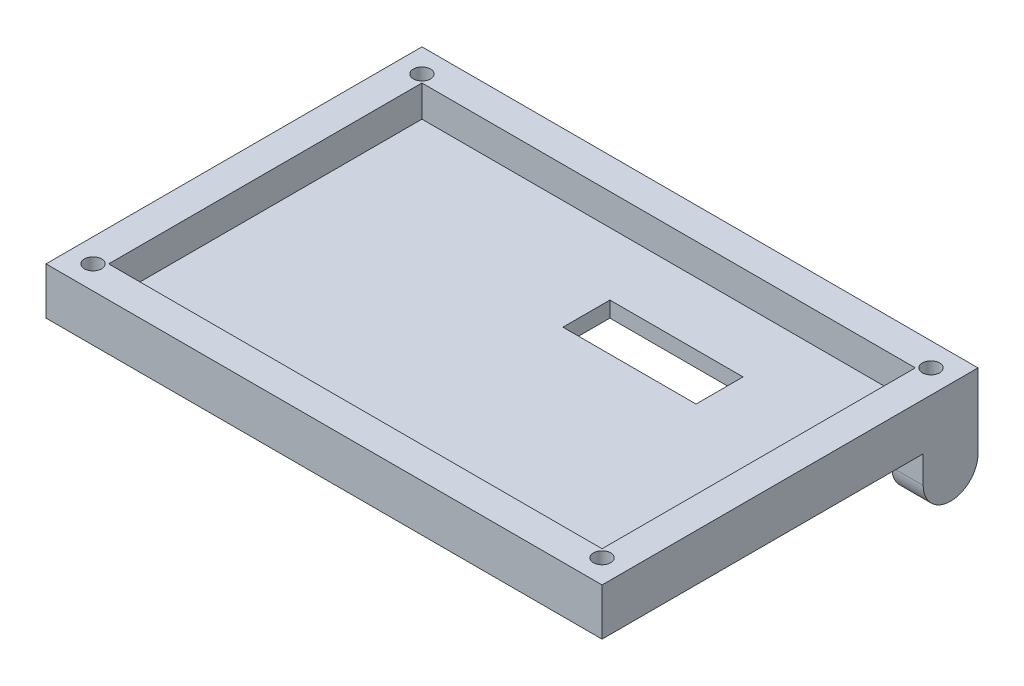
SolidWorks part; units mm, degrees
ref_plane "前视基准面" through (0, 0, 0) normal (0, 0, 1) x (1, 0, 0)
ref_plane "上视基准面" through (0, 0, 0) normal (0, 1, 0) x (1, 0, 0)
ref_plane "右视基准面" through (0, 0, 0) normal (1, 0, 0) x (0, 0, -1)
sketch "草图1" plane through (0, 0, 0) normal (0, 1, 0) x (1, 0, 0)
  line L1 (-17.75, 12) -> (17.75, 12)
  line L2 (-17.75, 12) -> (-17.75, -12)
  line L3 (-17.75, -12) -> (17.75, -12)
  line L4 (17.75, 12) -> (17.75, -12)
  line L5 (-17.75, 12) -> (17.75, -12) construction
  line L6 (-17.75, -12) -> (17.75, 12) construction
  point P0 (0, 0)
  dimension "D1" = 24
  dimension "D2" = 35.5
extrude "凸台-拉伸1" add sketch "草图1" along normal blind 3
sketch "草图2" plane through (0, 3, 0) normal (0, 1, 0) x (1, 0, 0)
  line L0 (17.75, 12) -> (-17.75, 12) construction
  line L1 (-15.75, 10) -> (15.75, 10)
  line L2 (-15.75, 10) -> (-15.75, -10)
  line L3 (-15.75, -10) -> (15.75, -10)
  line L4 (15.75, 10) -> (15.75, -10)
  line L5 (-15.75, 10) -> (15.75, -10) construction
  line L6 (-15.75, -10) -> (15.75, 10) construction
  line L7 (-17.75, 12) -> (-17.75, -12) construction
  point P0 (0, 0)
  dimension "D1" = 2
  dimension "D2" = 2
extrude "切除-拉伸1" cut sketch "草图2" against normal blind 2
sketch "草图3" plane through (0, 3, 0) normal (0, 1, 0) x (1, 0, 0)
  line L0 (17.75, 12) -> (-17.75, 12) construction
  line L1 (-17.75, 12) -> (-17.75, -12) construction
  line L2 (-17.75, -12) -> (17.75, -12) construction
  line L3 (17.75, -12) -> (17.75, 12) construction
  circle A0 centre (-16.25, 10.5) radius 0.55
  circle A1 centre (-16.25, -10.5) radius 0.55
  circle A2 centre (16.25, -10.5) radius 0.55
  circle A3 centre (16.25, 10.5) radius 0.55
  dimension "D3" = 1.1
  dimension "D10" = 1.1
  dimension "D11" = 1.1
  dimension "D12" = 1.1
  dimension "D1" = 1.5
  dimension "D2" = 1.5
  dimension "D4" = 1.5
  dimension "D5" = 1.5
  dimension "D6" = 1.5
  dimension "D7" = 1.5
  dimension "D8" = 1.5
  dimension "D9" = 1.5
extrude "切除-拉伸2" cut sketch "草图3" against normal blind 2
sketch "草图4" plane through (0, 0, 0) normal (0, -1, 0) x (1, 0, 0)
  line L1 (-17.75, -12) -> (-15.75, -12)
  line L2 (-17.75, -12) -> (-17.75, -8.5)
  line L3 (-17.75, -8.5) -> (-15.75, -8.5)
  line L4 (-15.75, -12) -> (-15.75, -8.5)
  line L5 (17.75, -12) -> (15.75, -12)
  line L6 (17.75, -12) -> (17.75, -8.5)
  line L7 (17.75, -8.5) -> (15.75, -8.5)
  line L8 (15.75, -12) -> (15.75, -8.5)
  dimension "D1" = 3.5
  dimension "D2" = 2
  dimension "D3" = 2
  dimension "D4" = 3.5
extrude "凸台-拉伸2" add sketch "草图4" along normal blind 3.5
sketch "草图5" plane through (-17.75, 0, 0) normal (-1, 0, 0) x (0, 0, 1)
  line L1 (-12, 3) -> (-12, -3.5) construction
  line L2 (-12, -1.75) -> (-12, -3.5)
  line L5 (-10.25, -3.5) -> (-12, -3.5)
  arc A1 (-12, -1.75) -> (-10.25, -3.5) centre (-10.25, -1.75) ccw
  dimension "D1" = 1.75
extrude "切除-拉伸3" cut sketch "草图5" against normal blind 2
sketch "草图6" plane through (-17.75, 0, 0) normal (-1, 0, 0) x (0, 0, 1)
  line L0 (-8.5, -3.5) -> (-10.25, -3.5)
  line L1 (-8.5, -3.5) -> (-10.25, -3.5) construction
  line L2 (-8.5, -3.5) -> (-8.5, 0) construction
  line L3 (-8.5, -3.5) -> (-8.5, -1.75)
  arc A0 (-12, -1.75) -> (-10.25, -3.5) centre (-10.25, -1.75) ccw construction
  arc A1 (-10.25, -3.5) -> (-8.5, -1.75) centre (-10.25, -1.75) ccw
extrude "切除-拉伸4" cut sketch "草图6" against normal blind 2
sketch "草图7" plane through (17.75, 0, 0) normal (1, 0, 0) x (0, 0, -1)
  line L0 (8.5, -3.5) -> (10.25, -3.5)
  line L1 (12, -3.5) -> (8.5, -3.5) construction
  line L2 (8.5, -3.5) -> (8.5, 0) construction
  line L3 (8.5, -1.75) -> (8.5, -3.5)
  arc A0 (10.25, -3.5) -> (8.5, -1.75) centre (10.25, -1.75) cw
extrude "切除-拉伸5" cut sketch "草图7" against normal blind 2
sketch "草图8" plane through (17.75, 0, 0) normal (1, 0, 0) x (0, 0, -1)
  line L0 (12, -3.5) -> (10.25, -3.5)
  line L1 (12, 3) -> (12, -3.5) construction
  line L2 (12, -1.75) -> (12, -3.5)
  arc A0 (10.25, -3.5) -> (12, -1.75) centre (10.25, -1.75) ccw
extrude "切除-拉伸6" cut sketch "草图8" against normal blind 2
sketch "草图10" plane through (15.75, 0, 0) normal (-1, 0, 0) x (0, 0, 1)
  line L0 (-8.5, -1.75) -> (-8.5, 0) construction
  line L1 (12, 0) -> (-8.5, 0) construction
  circle A0 centre (-10.25, -1.75) radius 0.6
  dimension "D1" = 1.2
  dimension "D2" = 1.75
  dimension "D3" = 1.75
extrude "切除-拉伸8" cut sketch "草图10" against normal blind 1.5
sketch "草图11" plane through (0, 0, 0) normal (0, -1, 0) x (1, 0, 0)
  line L1 (0.25, -3) -> (8.75, -3)
  line L2 (0.25, -3) -> (0.25, -6)
  line L3 (0.25, -6) -> (8.75, -6)
  line L4 (8.75, -3) -> (8.75, -6)
  line L5 (15.75, -8.5) -> (15.75, -12) construction
  line L6 (15.75, -12) -> (-15.75, -12) construction
  dimension "D1" = 7
  dimension "D2" = 8.5
  dimension "D3" = 3
  dimension "D4" = 6
extrude "切除-拉伸9" cut sketch "草图11" against normal blind 2
sketch "草图12" plane through (-15.75, 0, 0) normal (1, 0, 0) x (0, 0, -1)
  line L0 (12, -1.75) -> (12, 0) construction
  line L1 (12, 0) -> (8.5, 0) construction
  circle A0 centre (10.25, -1.75) radius 0.6
  dimension "D1" = 1.2
  dimension "D2" = 1.75
  dimension "D3" = 1.75
extrude "切除-拉伸10" cut sketch "草图12" against normal blind 1.5
